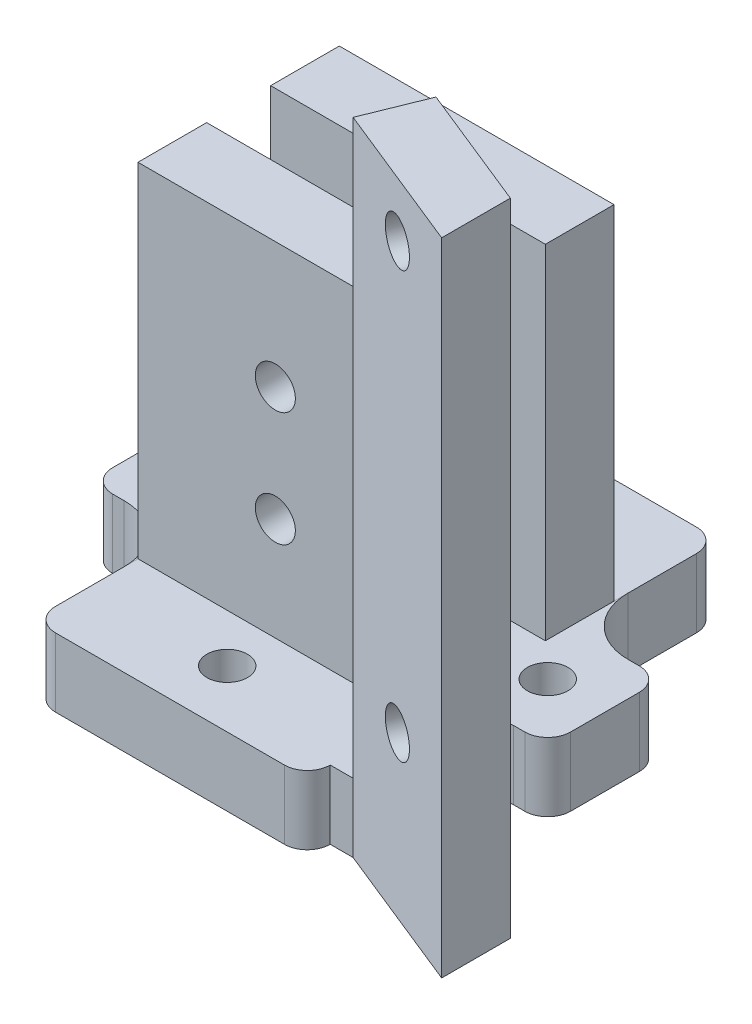
SolidWorks part; units mm, degrees
ref_plane "Front Plane" through (0, 0, 0) normal (0, 0, 1) x (1, 0, 0)
ref_plane "Top Plane" through (0, 0, 0) normal (0, 1, 0) x (1, 0, 0)
ref_plane "Right Plane" through (0, 0, 0) normal (1, 0, 0) x (0, 0, -1)
sketch "Sketch1" plane through (0, 0, 0) normal (0, 1, 0) x (1, 0, 0)
  line L1 (-10.1033, 11.3321) -> (13.8967, 11.3321)
  line L2 (-10.1033, 11.3321) -> (-10.1033, -12.6679)
  line L3 (-10.1033, -12.6679) -> (13.8967, -12.6679)
  line L4 (13.8967, 11.3321) -> (13.8967, -12.6679)
  dimension "D1" = 24
  dimension "D2" = 24
extrude "Boss-Extrude1" add sketch "Sketch1" along normal blind 6
sketch "Sketch2" plane through (0, 6, 0) normal (0, 1, 0) x (1, 0, 0)
  line L0 (-10.1033, 11.3321) -> (-10.1033, -12.6679) construction
  line L1 (-10.1033, -9.4629) -> (13.8967, -9.4629)
  line L2 (-10.1033, -9.4629) -> (-10.1033, -3.4629)
  line L3 (-10.1033, -3.4629) -> (13.8967, -3.4629)
  line L4 (13.8967, -9.4629) -> (13.8967, -3.4629)
  line L5 (13.8967, -12.6679) -> (13.8967, 11.3321) construction
  line L6 (-18.4237, -0.6679) -> (25.1046, -0.6679) construction
  line L7 (-10.1033, 2.1271) -> (13.8967, 2.1271)
  line L8 (-10.1033, 2.1271) -> (-10.1033, 8.1271)
  line L9 (-10.1033, 8.1271) -> (13.8967, 8.1271)
  line L10 (13.8967, 2.1271) -> (13.8967, 8.1271)
  dimension "D1" = 5.59
  dimension "D2" = 6
extrude "Boss-Extrude2" add sketch "Sketch2" along normal blind 30
sketch "Sketch3" plane through (0, 0, 12.6679) normal (0, 0, 1) x (1, 0, 0)
  line L4 (-10.1033, 0) -> (13.8967, 0)
  line L5 (13.8967, 0) -> (13.8967, 6)
  line L6 (13.8967, 6) -> (-10.1033, 6)
  line L7 (-10.1033, 6) -> (-10.1033, 0)
  line L8 (-10.1033, 0) -> (13.8967, 0)
  line L9 (13.8967, 0) -> (13.8967, 6)
  line L10 (13.8967, 6) -> (-10.1033, 6)
  line L11 (-10.1033, 6) -> (-10.1033, 0)
  dimension "D1" = 0
extrude "Boss-Extrude3" add sketch "Sketch3" along normal blind 6
sketch "Sketch4" plane through (0, 0, -11.3321) normal (0, 0, -1) x (-1, 0, 0)
  line L4 (-13.8967, 0) -> (10.1033, 0)
  line L5 (10.1033, 0) -> (10.1033, 6)
  line L6 (10.1033, 6) -> (-13.8967, 6)
  line L7 (-13.8967, 6) -> (-13.8967, 0)
  line L8 (-13.8967, 0) -> (10.1033, 0)
  line L9 (10.1033, 0) -> (10.1033, 6)
  line L10 (10.1033, 6) -> (-13.8967, 6)
  line L11 (-13.8967, 6) -> (-13.8967, 0)
  dimension "D1" = 0
extrude "Boss-Extrude4" add sketch "Sketch4" along normal blind 6
sketch "Sketch5" plane through (13.8967, 0, 0) normal (1, 0, 0) x (0, 0, -1)
  line L0 (-0.6679, 21.637) -> (-0.6679, 0) construction
  line L1 (-18.6679, 0) -> (17.3321, 0) construction
  line L2 (-3.4629, 6) -> (2.1271, 6) construction
  line L3 (-5.6679, 0) -> (4.3321, 0)
  line L4 (-5.6679, 0) -> (-5.6679, 6)
  line L5 (-5.6679, 6) -> (4.3321, 6)
  line L6 (4.3321, 0) -> (4.3321, 6)
  dimension "D1" = 10
extrude "Boss-Extrude5" add sketch "Sketch5" along normal blind 8
fillet "Fillet1" radius 5 2 edges
fillet "Fillet2" radius 2 2 edges at (21.8967, 3, -4.3321) (21.8967, 3, 5.6679)
fillet "Fillet3" radius 2 4 edges at (-10.1033, 3, -17.3321) (13.8967, 3, -17.3321) (-10.1033, 3, 18.6679) (13.8967, 3, 18.6679)
sketch "Sketch6" plane through (-10.1033, 0, 0) normal (-1, 0, 0) x (0, 0, 1)
  line L0 (0.6679, 0) -> (0.6679, 18.2836) construction
  line L1 (-15.3321, 0) -> (16.6679, 0) construction
  line L2 (-2.1271, 6) -> (3.4629, 6) construction
  line L3 (-4.3321, 0) -> (5.6679, 0)
  line L4 (-4.3321, 0) -> (-4.3321, 6)
  line L5 (-4.3321, 6) -> (5.6679, 6)
  line L6 (5.6679, 0) -> (5.6679, 6)
  dimension "D1" = 10
extrude "Boss-Extrude6" add sketch "Sketch6" along normal blind 8
fillet "Fillet4" radius 5 2 edges at (-10.1033, 3, 5.6679) (-10.1033, 3, -4.3321)
fillet "Fillet5" radius 2 2 edges at (-18.1033, 3, 5.6679) (-18.1033, 3, -4.3321)
sketch "Sketch7" plane through (0, 6, 0) normal (0, 1, 0) x (1, 0, 0)
  line L2 (-18.1033, -0.6679) -> (21.8967, -0.6679) construction
  line L3 (1.8967, -18.6679) -> (1.8967, 17.3321) construction
  line L4 (11.8967, -18.6679) -> (-8.1033, -18.6679) construction
  line L5 (-8.1033, 17.3321) -> (11.8967, 17.3321) construction
  line L6 (-18.1033, -3.6679) -> (-18.1033, 2.3321) construction
  line L7 (21.8967, 2.3321) -> (21.8967, -3.6679) construction
  circle A0 centre (1.8967, -13.6679) radius 1.775
  circle A2 centre (-13.1033, -0.6679) radius 1.775
  circle A3 centre (1.8967, 12.3321) radius 1.775
  circle A4 centre (16.8967, -0.6679) radius 1.775
  dimension "D5" = 3.55
  dimension "D1" = 5
  dimension "D2" = 5
  dimension "D3" = 5
  dimension "D4" = 5
extrude "Cut-Extrude1" cut sketch "Sketch7" against normal through all
sketch "Sketch8" plane through (13.8967, 0, 0) normal (1, 0, 0) x (0, 0, -1)
  line L4 (-10.6679, 6) -> (-16.6679, 6)
  line L5 (-16.6679, 6) -> (-16.6679, 0)
  line L6 (-16.6679, 0) -> (-10.6679, 0)
  line L7 (-10.6679, 0) -> (-10.6679, 6)
  line L8 (-10.6679, 6) -> (-16.6679, 6)
  line L9 (-16.6679, 6) -> (-16.6679, 0)
  line L10 (-16.6679, 0) -> (-10.6679, 0)
  line L11 (-10.6679, 0) -> (-10.6679, 6)
  dimension "D1" = 0
extrude "Boss-Extrude7" add sketch "Sketch8" along normal blind 2
sketch "Sketch9" plane through (0, 6, 0) normal (0, 1, 0) x (1, 0, 0)
  line L0 (15.8967, -10.6679) -> (39.9644, -20.3919) construction
  line L1 (15.8967, -10.6679) -> (15.8967, -16.6679) construction
  dimension "D1" = 68
sketch "Sketch10" plane through (15.8967, 0, 0) normal (1, 0, 0) x (0, 0, -1)
  line L4 (-10.6679, 0) -> (-10.6679, 6)
  line L5 (-10.6679, 6) -> (-16.6679, 6)
  line L6 (-16.6679, 6) -> (-16.6679, 0)
  line L7 (-16.6679, 0) -> (-10.6679, 0)
  line L8 (-10.6679, 0) -> (-10.6679, 6)
  line L9 (-10.6679, 6) -> (-16.6679, 6)
  line L10 (-16.6679, 6) -> (-16.6679, 0)
  line L11 (-16.6679, 0) -> (-10.6679, 0)
  dimension "D1" = 0
extrude "Boss-Extrude8" add sketch "Sketch10" along direction (0.9272, 0, 0.3746) on the side of the normal blind 14
sketch "Sketch11" plane through (0, 6, 0) normal (0, 1, 0) x (1, 0, 0)
  line L0 (28.8773, -21.9124) -> (15.8967, -16.6679)
  line L1 (28.8773, -21.9124) -> (15.8967, -16.6679) construction
  line L2 (15.8967, -16.6679) -> (17.9807, -11.5099)
  line L3 (17.9807, -11.5099) -> (28.8773, -15.9124)
  line L4 (28.8773, -15.9124) -> (28.8773, -21.9124)
  line L5 (28.8773, -15.9124) -> (28.8773, -21.9124) construction
  line L6 (15.8967, -10.6679) -> (39.9644, -20.3919) construction
  dimension "D1" = 14
extrude "Boss-Extrude9" add sketch "Sketch11" along normal blind 50
sketch "Sketch12" plane through (-3.5585, 0, 8.8075) normal (-0.3746, 0, 0.9272) x (0.9272, 0, 0.3746)
  line L0 (27.9831, 56) -> (27.9831, 0) construction
  line L1 (20.9831, 56) -> (34.9831, 56) construction
  line L2 (34.9831, 0) -> (20.9831, 0) construction
  circle A0 centre (27.9831, 14) radius 1.905
  circle A1 centre (27.9831, 51.211) radius 1.905
  dimension "D1" = 3.81
  dimension "D2" = 37.211
  dimension "D3" = 14
extrude "Cut-Extrude2" cut sketch "Sketch12" against normal through all
sketch "Sketch13" plane through (0, 0, 9.4629) normal (0, 0, 1) x (1, 0, 0)
  line L0 (1.8967, 15) -> (1.8967, 25) construction
  line L1 (1.8967, 25) -> (1.8967, 36) construction
  line L2 (-10.1033, 36) -> (13.8967, 36) construction
  line L3 (-8.1033, 0) -> (11.8967, 0) construction
  circle A0 centre (1.8967, 15) radius 1.75
  circle A1 centre (1.8967, 25) radius 1.75
  dimension "D1" = 3.5
  dimension "D2" = 15
  dimension "D3" = 25
extrude "Cut-Extrude3" cut sketch "Sketch13" against normal up to surface (17.59 mm away) up to face at (1.8967, 21, -8.1271)
